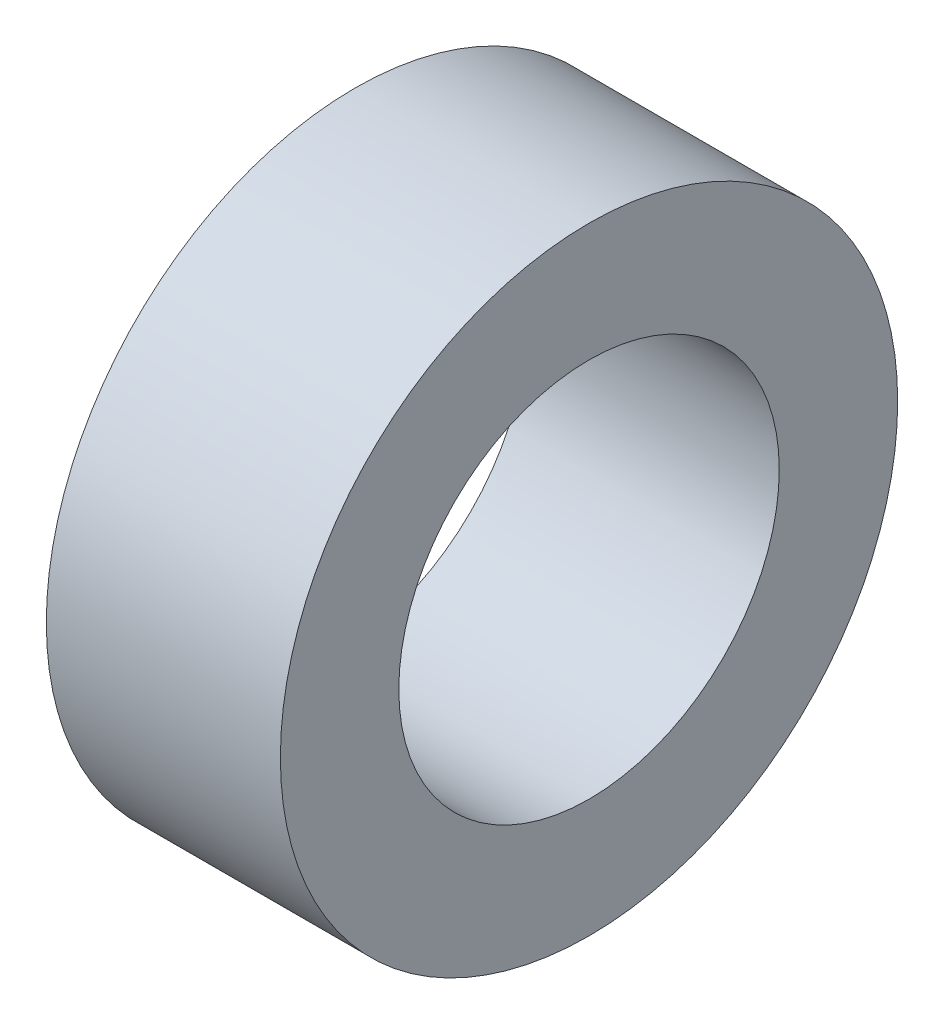
SolidWorks part; units mm, degrees
material "Nylon 101"
ref_plane "Front Plane" through (0, 0, 0) normal (0, 0, 1) x (1, 0, 0)
ref_plane "Top Plane" through (0, 0, 0) normal (0, 1, 0) x (1, 0, 0)
ref_plane "Right Plane" through (0, 0, 0) normal (1, 0, 0) x (0, 0, -1)
sketch "Sketch1" plane through (0, 0, 0) normal (1, 0, 0) x (0, 0, -1)
  circle A0 centre (0, 0) radius 10.2
  circle A1 centre (0, 0) radius 11.9011
  dimension "D1" = 20.4
  dimension "D2" = 23.8022
extrude "Boss-Extrude1" add sketch "Sketch1" along normal blind 1
sketch "Sketch2" plane through (1, 0, 0) normal (1, 0, 0) x (0, 0, -1)
  circle A0 centre (0, 0) radius 16.55
  circle A1 centre (0, 0) radius 10.2 construction
  circle A2 centre (0, 0) radius 10.2
  dimension "D1" = 6.35
extrude "Boss-Extrude2" add sketch "Sketch2" along normal blind 12.55
equation "\"D2@Sketch1\"=11.9011mm*2"
equation "\"D1@Boss-Extrude1\"=1mm"
equation "\"D1@Boss-Extrude2\"=18.9mm-.25in"
